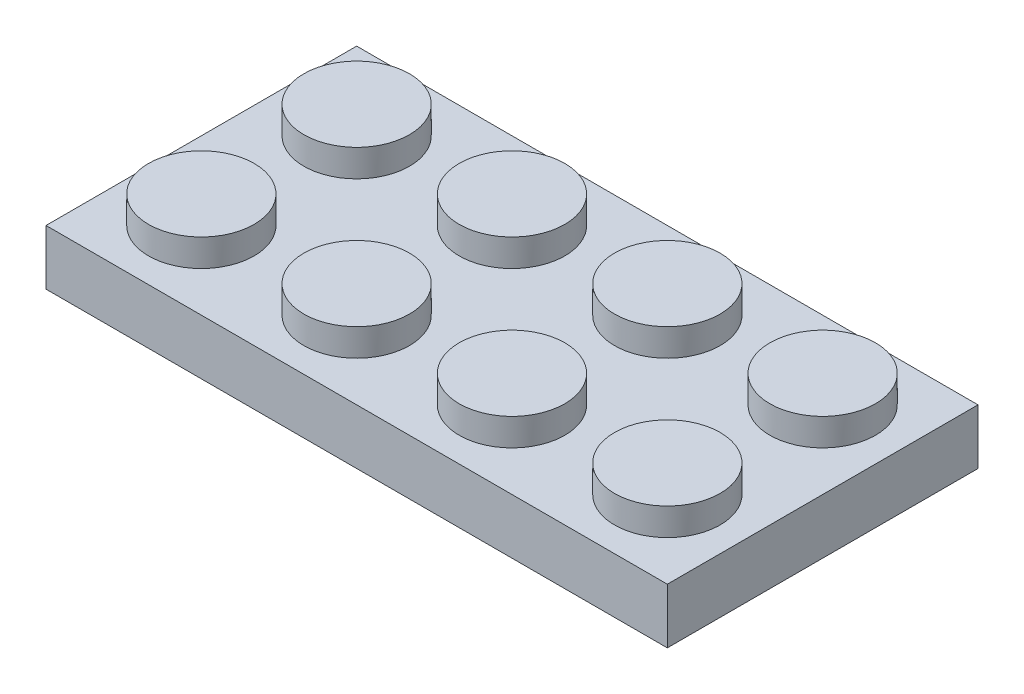
SolidWorks part; units mm, degrees
note: The reader was unsure of these and kept them because the rebuilt part matched: shared geometry of "Sketch2<3>".
ref_plane "Front Plane" through (0, 0, 0) normal (0, 0, 1) x (1, 0, 0)
ref_plane "Top Plane" through (0, 0, 0) normal (0, 1, 0) x (1, 0, 0)
ref_plane "Right Plane" through (0, 0, 0) normal (1, 0, 0) x (0, 0, -1)
sketch "Sketch1" plane through (0, 0, 0) normal (0, 1, 0) x (1, 0, 0)
  line L1 (15.875, 7.9375) -> (-15.875, 7.9375)
  line L2 (15.875, 7.9375) -> (15.875, -7.9375)
  line L3 (15.875, -7.9375) -> (-15.875, -7.9375)
  line L4 (-15.875, 7.9375) -> (-15.875, -7.9375)
  line L5 (15.875, 7.9375) -> (-15.875, -7.9375) construction
  line L6 (15.875, -7.9375) -> (-15.875, 7.9375) construction
  point P0 (0, 0)
  dimension "D1" = 15.875
  dimension "D2" = 31.75
extrude "Boss-Extrude1" add sketch "Sketch1" along normal mid plane 2.8194
sketch "Sketch2" plane through (0, -1.4097, 0) normal (0, -1, 0) x (1, 0, 0)
  line L8 (-14.605, 6.6675) -> (-14.605, -6.6675)
  line L9 (-14.605, -6.6675) -> (14.605, -6.6675)
  line L10 (14.605, -6.6675) -> (14.605, 6.6675)
  line L11 (14.605, 6.6675) -> (-14.605, 6.6675)
  line L12 (-14.605, 6.6675) -> (-14.605, -6.6675)
  line L13 (-14.605, -6.6675) -> (14.605, -6.6675)
  line L14 (14.605, -6.6675) -> (14.605, 6.6675)
  line L15 (14.605, 6.6675) -> (-14.605, 6.6675)
  circle A0 centre (0, 0) radius 3.175
  circle A1 centre (0, 0) radius 2.413
  dimension "D2" = 6.35
  dimension "D3" = 4.826
  dimension "D1" = 1.27
extrude "Cut-Extrude1" cut sketch "Sketch2" against normal offset from surface (1.5494 mm away) 1.27 contours L14 L15 L12 L13 A0 | A1 | A0 A1 up to face at (0, 1.4097, 0)
sketch "Sketch3" plane through (0, 1.4097, 0) normal (0, 1, 0) x (1, 0, 0)
  line L0 (15.875, -7.9375) -> (15.875, 7.9375) construction
  line L1 (-15.875, -7.9375) -> (15.875, -7.9375) construction
  circle A0 centre (11.9062, -3.9688) radius 2.6987
  dimension "D1" = 5.3975
  dimension "D2" = 3.9688
  dimension "D3" = 3.9688
extrude "Boss-Extrude2" add sketch "Sketch3" along normal blind 1.397
pattern_linear "LPattern1" count 4 spacing 7.9375 along (-1, 0, 0) count 2 spacing 7.9375 along (0, 0, -1) of "Boss-Extrude2"
extrude "Boss-Extrude3" add sketch "Sketch2<3>" against normal up to surface (1.5494 mm away) contours A0 A1 | A1
sketch "Sketch2<3>" plane through (0, -1.4097, 0) normal (0, -1, 0) x (1, 0, 0) same geometry as "Sketch2"
pattern_linear "LPattern2" count 2 spacing 7.9375 along (1, 0, 0) count 2 spacing 7.9375 along (-1, 0, 0) of "Boss-Extrude3"
